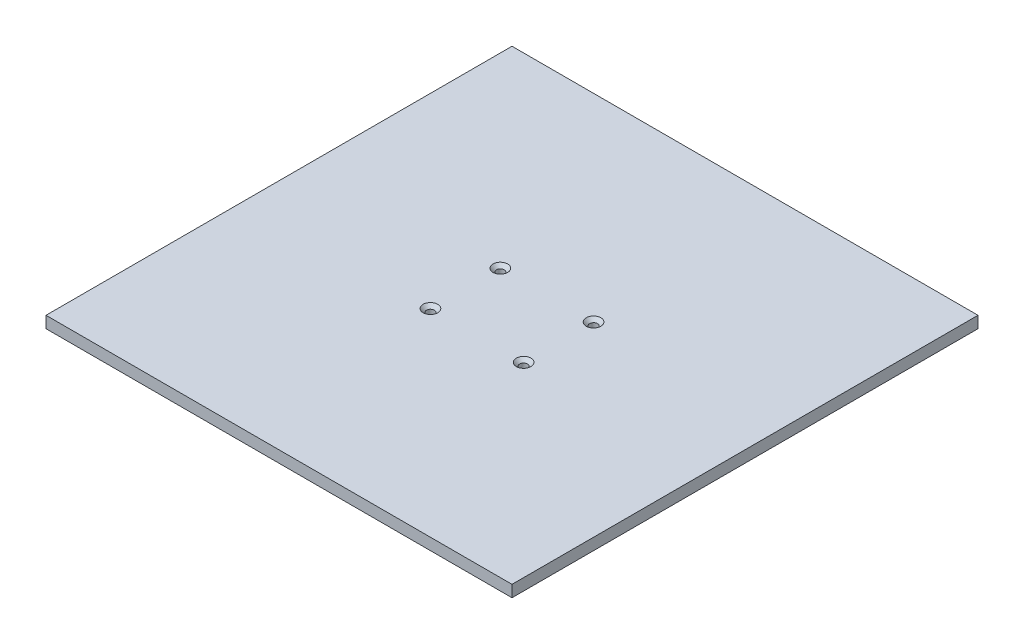
SolidWorks part; units mm, degrees
ref_plane "Front Plane" through (0, 0, 0) normal (0, 0, 1) x (1, 0, 0)
ref_plane "Top Plane" through (0, 0, 0) normal (0, 1, 0) x (1, 0, 0)
ref_plane "Right Plane" through (0, 0, 0) normal (1, 0, 0) x (0, 0, -1)
sketch "Sketch1" plane through (0, 0, 0) normal (0, 1, 0) x (1, 0, 0)
  line L1 (-100, -100) -> (100, -100)
  line L2 (-100, -100) -> (-100, 100)
  line L3 (-100, 100) -> (100, 100)
  line L4 (100, -100) -> (100, 100)
  line L5 (-100, -100) -> (100, 100) construction
  line L6 (-100, 100) -> (100, -100) construction
  point P0 (0, 0)
  dimension "D1" = 200
extrude "Boss-Extrude1" add sketch "Sketch1" along normal mid plane 5
sketch "Sketch2" plane through (0, 2.5, 0) normal (0, 1, 0) x (1, 0, 0)
  line L1 (-20, -15) -> (20, -15) construction
  line L2 (-20, -15) -> (-20, 15) construction
  line L3 (-20, 15) -> (20, 15) construction
  line L4 (20, -15) -> (20, 15) construction
  line L5 (-20, -15) -> (20, 15) construction
  line L6 (-20, 15) -> (20, -15) construction
  point P0 (0, 0)
  dimension "D1" = 40
  dimension "D2" = 30
hole_wizard "CSK for M3 Flat Head Machine Screw1" positions "Sketch3" profile "Sketch4" countersink size "M3" standard "ANSI Metric" end condition up to next
sketch "Sketch3" plane through (0, 2.5, 0) normal (0, 1, 0) x (1, 0, 0)
  point P0 (-20, 15)
  point P3 (20, 15)
  point P6 (20, -15)
  point P9 (-20, -15)
sketch "Sketch4" plane through (-20, 2.5, -15) normal (1, 0, 0) x (0, 0, 1)
  line L0 (0, 0) -> (0, 5)
  line L1 (0, 5) -> (1.7, 5)
  line L2 (1.7, 5) -> (1.7, 1.45)
  line L3 (1.7, 1.45) -> (3.15, 0)
  line L5 (3.15, 0) -> (0, 0)
  line L6 (-1.7, 1.45) -> (-3.15, 0) construction
  line L11 (0, -6.35) -> (0, 107.95) construction
  dimension "Thru Hole Dia." = 3.4
  dimension "Thru Hole Depth" = 5
  dimension "Near C'Sink Dia." = 6.3
  dimension "Near C'Sink Angle" = 90
